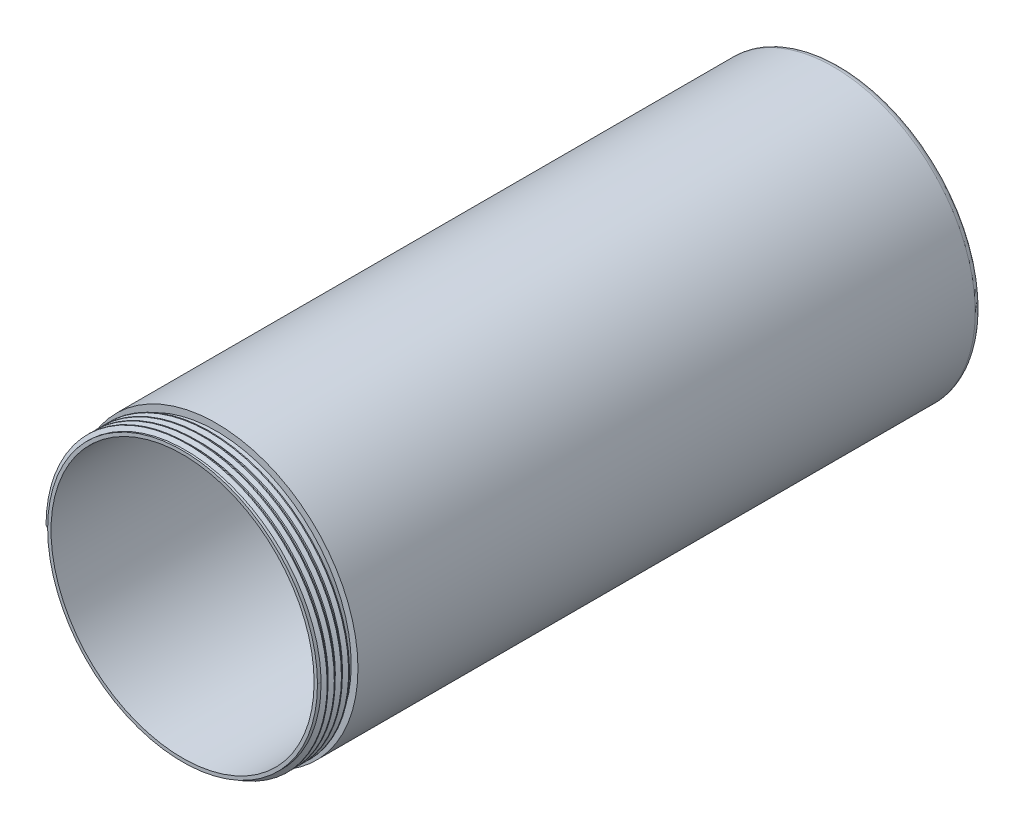
SolidWorks part; units mm, degrees
ref_plane "Front Plane" through (0, 0, 0) normal (0, 0, 1) x (1, 0, 0)
ref_plane "Top Plane" through (0, 0, 0) normal (0, 1, 0) x (1, 0, 0)
ref_plane "Right Plane" through (0, 0, 0) normal (1, 0, 0) x (0, 0, -1)
sketch "Sketch1" plane through (0, 0, 0) normal (0, 1, 0) x (1, 0, 0)
  circle A0 centre (0, 0) radius 42
  dimension "D1" = 84
extrude "Boss-Extrude1" add sketch "Sketch1" along normal blind 195 contours A0
sketch "Sketch2" plane through (0, 195, 0) normal (0, 1, 0) x (1, 0, 0)
  circle A0 centre (0, 0) radius 40
move or copy body "Body-Move/Copy1" bodies to move or copy 101 copy no translate (-42, 11.3402, 0)
move or copy body "Body-Move/Copy2" bodies to move or copy 104 copy no rotation origin (0, 108.8402, 0) rotation axis (1, 0, 0) rotation angle 90
move or copy body "Body-Move/Copy3" bodies to move or copy 105 copy no translate (-3.3007, -3.6422, -82.8031)
sketch "Sketch3" plane through (0, 0, 14.6969) normal (0, 0, 1) x (1, 0, 0)
  circle A2 centre (-45.3007, 105.198) radius 41
  circle A3 centre (-45.3007, 105.198) radius 41
  dimension "D1" = 1
fillet "Fillet1" radius 2 1 edges at (-45.3007, 63.198, -180.3031)
sketch "Sketch5" plane through (0, 0, 14.6969) normal (0, 0, 1) x (1, 0, 0)
  circle A2 centre (-45.3007, 105.198) radius 39
  circle A3 centre (-45.3007, 105.198) radius 39
  dimension "D1" = 3
extrude "Cut-Extrude1" cut sketch "Sketch5" against normal blind 190
sketch "Sketch6" plane through (0, 0, 14.6969) normal (0, 0, 1) x (1, 0, 0)
  circle A2 centre (-45.3007, 105.198) radius 40
  circle A3 centre (-45.3007, 105.198) radius 40
  dimension "D1" = 2
extrude "Cut-Extrude2" cut sketch "Sketch6" against normal blind 10 flip side to cut
thread "Thread1" pitch 2.1167 method extrude profile "Thread Profile1" start angle 0, offset 0, length 8, pitch 2.1167, diameter 80
ref_plane "Plane1" through (-85.3007, 105.198, 14.6969) normal (0, -1, 0) x (-1, 0, 0)
sketch "Thread Profile1" plane through (-85.3007, 105.198, 14.6969) normal (0, -1, 0) x (-1, 0, 0)
  line L0 (0, 0) -> (0, 2.1167) construction
  line L1 (0, 0) -> (1.1457, 0.6615)
  line L2 (1.1457, 0.6615) -> (1.1457, 0.926)
  line L3 (1.1457, 0.926) -> (0, 1.5875)
  line L4 (1.1457, 0.7937) -> (0, 0.7937) construction
  line L11 (0, 0) -> (0, 1.5875)
  point P2 (0, 0)
  dimension "Pitch" = 2.1167
  dimension "Profile_Angle" = 60
  dimension "Profile_Land" = 0.2646
  dimension "Profile_Height" = 1.1457
